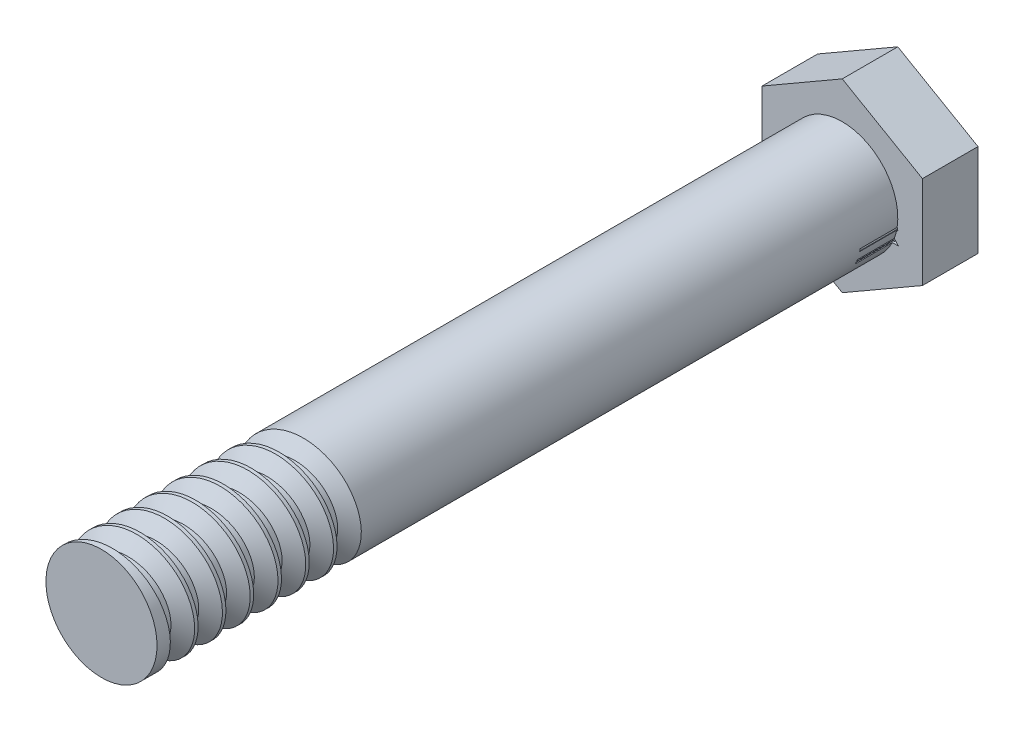
SolidWorks part; units mm, degrees
ref_plane "Front Plane" through (0, 0, 0) normal (0, 0, 1) x (1, 0, 0)
ref_plane "Top Plane" through (0, 0, 0) normal (0, 1, 0) x (1, 0, 0)
ref_plane "Right Plane" through (0, 0, 0) normal (1, 0, 0) x (0, 0, -1)
sketch "Sketch3" plane through (0, 0, 0) normal (0, 0, 1) x (1, 0, 0)
  line L1 (0, 5) -> (-4.3301, 2.5)
  line L2 (-4.3301, 2.5) -> (-4.3301, -2.5)
  line L3 (-4.3301, -2.5) -> (0, -5)
  line L4 (0, -5) -> (4.3301, -2.5)
  line L5 (4.3301, -2.5) -> (4.3301, 2.5)
  line L6 (4.3301, 2.5) -> (0, 5)
  circle A0 centre (0, 0) radius 4.3301 construction
  dimension "D1" = 10
extrude "Boss-Extrude3" add sketch "Sketch3" along normal blind 3
sketch "Sketch4" plane through (0, 0, 3) normal (0, 0, 1) x (1, 0, 0)
  circle A0 centre (0, 0) radius 3
  dimension "D1" = 6
extrude "Boss-Extrude4" add sketch "Sketch4" along normal blind 40
thread "Thread3" pitch 1.5 method cut profile "Thread Profile3" start angle 10, offset 0, length 10, pitch 1.5, diameter 6
ref_plane "Plane3" through (-2.9544, 0.5209, 43) normal (-0.1736, -0.9848, 0) x (-0.9848, 0.1736, 0)
sketch "Thread Profile3" plane through (-2.9544, 0.5209, 43) normal (-0.1736, -0.9848, 0) x (-0.9848, 0.1736, 0)
  line L0 (0, 0) -> (0, 1.5) construction
  line L11 (0, 0) -> (0, 1.3125)
  line L12 (0, 1.3125) -> (-0.8119, 0.8437)
  line L13 (-0.8119, 0.8437) -> (-0.8119, 0.4687)
  line L15 (-0.8119, 0.4687) -> (0, 0)
  line L17 (-0.8119, 0.6562) -> (0, 0.6562) construction
  point P2 (0, 0)
  dimension "Pitch" = 1.5
  dimension "Profile_Angle" = 60
  dimension "Profile_Land" = 0.375
  dimension "Profile_Height" = 0.8119
sketch "Sketch5" plane through (0, 0, 0) normal (0, 0, -1) x (-1, 0, 0)
  text T0 "20BME081" font "Century Gothic" height 1
extrude "Cut-Extrude1" cut sketch "Sketch5" against normal blind 5
